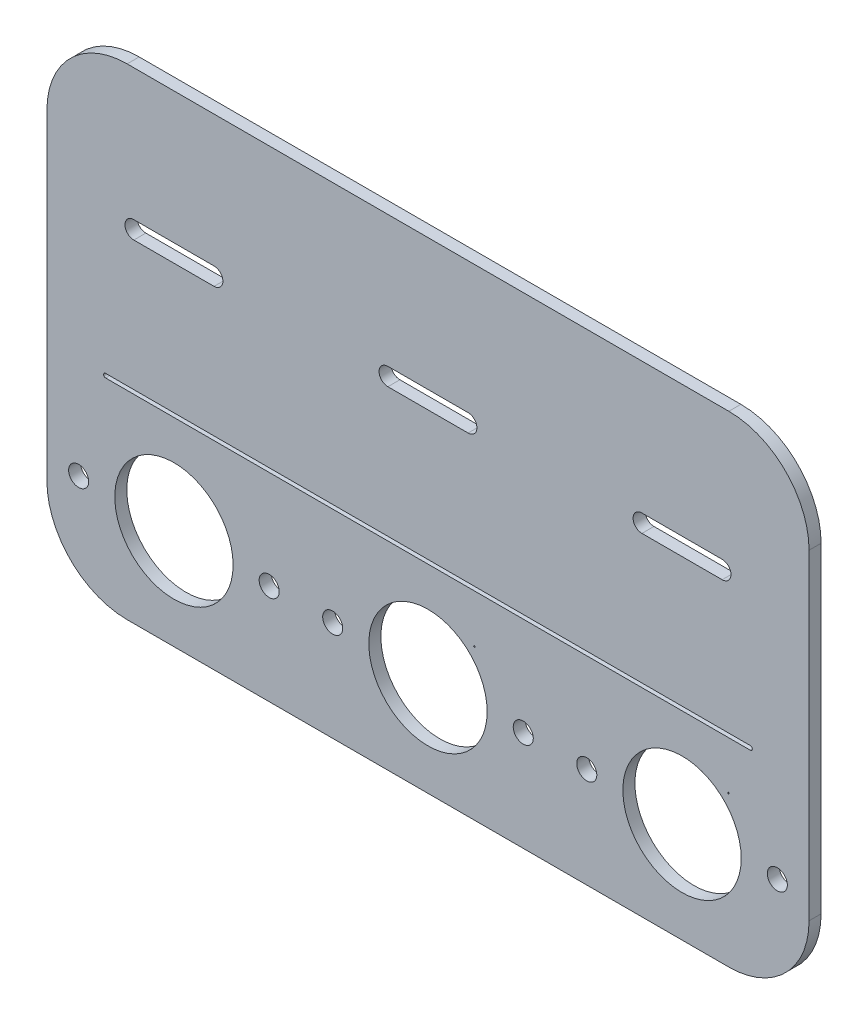
SolidWorks part; units mm, degrees
ref_plane "Front Plane" through (0, 0, 0) normal (0, 0, 1) x (1, 0, 0)
ref_plane "Top Plane" through (0, 0, 0) normal (0, 1, 0) x (1, 0, 0)
ref_plane "Right Plane" through (0, 0, 0) normal (1, 0, 0) x (0, 0, -1)
sketch "Sketch1" plane through (0, 0, 0) normal (0, 0, 1) x (1, 0, 0)
  line L1 (-95, 25) -> (95, 25)
  line L2 (-95, 25) -> (-95, -25)
  line L3 (-95, -25) -> (95, -25)
  line L4 (95, 25) -> (95, -25)
  line L5 (-95, 25) -> (95, -25) construction
  line L6 (-95, -25) -> (95, 25) construction
  point P0 (0, 0)
  dimension "D1" = 190
  dimension "D2" = 50
extrude "Boss-Extrude1" add sketch "Sketch1" along normal blind 3
sketch "Sketch2" plane through (0, 0, 3) normal (0, 0, 1) x (1, 0, 0)
  line L0 (-63.3333, 0) -> (-87.0833, 0) construction
  line L1 (-63.3333, 0) -> (-63.3333, 14.75) construction
  line L2 (-95, 25) -> (-95, -25) construction
  circle A0 centre (-63.3333, 0) radius 14.75
  circle A1 centre (11.5839, 12.5106) radius 0.1853
  circle A2 centre (-87.0833, 0) radius 2.5
  circle A3 centre (-39.5833, 0) radius 2.5
  dimension "D1" = 29.5
  dimension "D2" = 5
  dimension "D3" = 47.5
  dimension "D4" = 31.6667
extrude "Cut-Extrude1" cut sketch "Sketch2" against normal through all
pattern_linear "LPattern1" count 3 spacing 63.3333 along (1, 0, 0) of "Cut-Extrude1"
sketch "Sketch3" plane through (0, 0, 3) normal (0, 0, 1) x (1, 0, 0)
  line L0 (95, 60) -> (-95, 60) construction
  line L1 (95, 25) -> (-95, 25)
  line L2 (95, 25) -> (95, 95)
  line L3 (95, 95) -> (-95, 95)
  line L4 (-95, 25) -> (-95, 95)
  line L5 (73.3333, 60) -> (53.3333, 60) construction
  line L8 (73.3333, 57.8) -> (53.3333, 57.8)
  line L11 (73.3333, 62.2) -> (53.3333, 62.2)
  arc A4 (73.3333, 57.8) -> (73.3333, 62.2) centre (73.3333, 60) ccw
  arc A5 (53.3333, 62.2) -> (53.3333, 57.8) centre (53.3333, 60) ccw
  point P10 (63.3333, 60)
  dimension "D2" = 2.2
  dimension "D1" = 70
  dimension "D3" = 20
  dimension "D4" = 31.6667
extrude "Boss-Extrude2" add sketch "Sketch3" against normal up to surface (3 mm away) contours L2 L1 L4 L3 up to face at (78.0833, 0, 0)
extrude "Cut-Extrude2" cut sketch "Sketch3<3>" against normal up to surface (3 mm away) contours L11 A5 L8 A4 region at (63.3333, 60, 3) up to face at (78.0833, 0, 0)
sketch "Sketch3<3>" plane through (0, 0, 3) normal (0, 0, 1) x (1, 0, 0) same geometry as "Sketch3"
pattern_linear "LPattern2" count 3 spacing 63.3333 along (-1, 0, 0) of "Cut-Extrude2"
sketch "Sketch4" plane through (0, 0, 3) normal (0, 0, 1) x (1, 0, 0)
  line L0 (-95, 25) -> (95, 25) construction
  line L1 (95, -25) -> (95, 95) construction
  line L3 (87.0833, 0) -> (95, 0) construction
  line L4 (-95, -25) -> (95, -25) construction
  line L5 (-95, -25) -> (95, -25)
  line L6 (-95, 95) -> (-95, -25) construction
  line L7 (80.3613, 25) -> (-80.3613, 25) construction
  line L8 (80.3613, 24.5) -> (-80.3613, 24.5)
  line L9 (80.3613, 25.5) -> (-80.3613, 25.5)
  arc A0 (80.3613, 24.5) -> (80.3613, 25.5) centre (80.3613, 25) ccw
  arc A1 (-80.3613, 25.5) -> (-80.3613, 24.5) centre (-80.3613, 25) ccw
  point P14 (0, 25)
  dimension "D2" = 0.5
  dimension "D1" = 50
extrude "Cut-Extrude3" cut sketch "Sketch4" against normal blind 1 contours L9 A1 L8 A0 region at (0, 25, 3)
fillet "Fillet1" radius 20 2 edges at (95, -25, 1.5) (-95, -25, 1.5)
fillet "Fillet2" radius 20 2 edges at (95, 95, 1.5) (-95, 95, 1.5)
sketch "Sketch5" [suppressed] plane through (0, 0, 3) normal (0, 0, 1) x (1, 0, 0)
  line L0 (95, 25.5) -> (-95, 25.5) construction
  line L1 (95, -5) -> (95, 75) construction
  line L2 (-95, 75) -> (-95, -5) construction
  line L3 (80.3613, 25.5) -> (-80.3613, 25.5) construction
